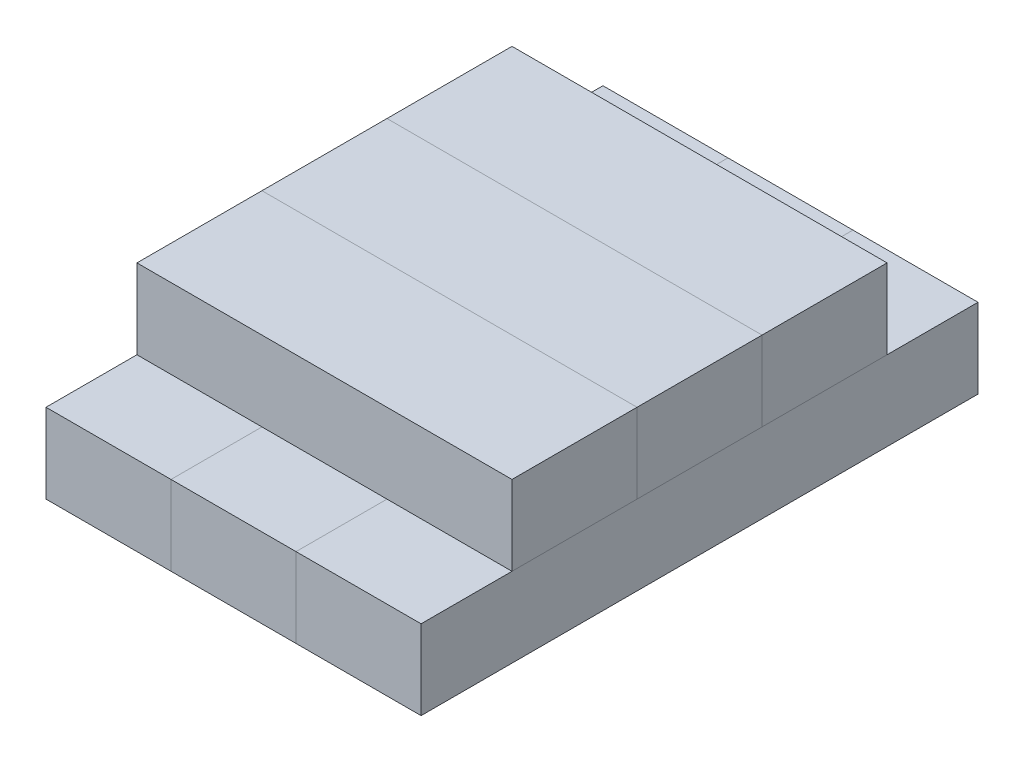
SolidWorks part; units mm, degrees
other "Markup1"
sketch "Sketch3" plane through (419.1, 177.8, 622.3) normal (0.8218, 0.5697, 0.0127) x (-0.0081, 0.0339, -0.9994)
material "Pine"
ref_plane "Front Plane" through (0, 0, 0) normal (0, 0, 1) x (1, 0, 0)
ref_plane "Top Plane" through (0, 0, 0) normal (0, 1, 0) x (1, 0, 0)
ref_plane "Right Plane" through (0, 0, 0) normal (1, 0, 0) x (0, 0, -1)
sketch "Sketch1" plane through (0, 0, 0) normal (0, 0, 1) x (1, 0, 0)
  line L1 (0, 0) -> (139.7, 0)
  line L2 (0, 0) -> (0, 88.9)
  line L3 (0, 88.9) -> (139.7, 88.9)
  line L4 (139.7, 0) -> (139.7, 88.9)
  line L5 (139.7, 0) -> (279.4, 0)
  line L6 (139.7, 0) -> (139.7, 88.9)
  line L7 (139.7, 88.9) -> (279.4, 88.9)
  line L8 (279.4, 0) -> (279.4, 88.9)
  line L9 (279.4, 0) -> (419.1, 0)
  line L10 (279.4, 0) -> (279.4, 88.9)
  line L11 (279.4, 88.9) -> (419.1, 88.9)
  line L12 (419.1, 0) -> (419.1, 88.9)
  dimension "D1" = 88.9
  dimension "D2" = 139.7
  dimension "D3" = 139.7
  dimension "D4" = 139.7
extrude "Boss-Extrude1" add sketch "Sketch1" along normal blind 622.3 contours L1 L4 L3 L2 | L9 L12 L11 L8 region at (69.85, 44.45, 0) region at (349.25, 44.45, 0)
extrude "Boss-Extrude2" add sketch "Sketch1<4>" along normal up to surface (622.3 mm away) separate body contours L5 L8 L7 L4 region at (209.55, 44.45, 0) up to face at (69.85, 44.45, 622.3)
sketch "Sketch1<4>" plane through (0, 0, 0) normal (0, 0, 1) x (1, 0, 0) same geometry as "Sketch1"
sketch "Sketch2" plane through (0, 0, 0) normal (1, 0, 0) x (0, 0, -1)
  line L0 (-622.3, 88.9) -> (0, 88.9) construction
  line L1 (-520.7, 88.9) -> (-381, 88.9)
  line L2 (-520.7, 88.9) -> (-520.7, 177.8)
  line L3 (-520.7, 177.8) -> (-381, 177.8)
  line L4 (-381, 88.9) -> (-381, 177.8)
  line L5 (-622.3, 0) -> (-622.3, 88.9) construction
  dimension "D1" = 88.9
  dimension "D2" = 139.7
  dimension "D3" = 101.6
extrude "Boss-Extrude3" add sketch "Sketch2" along normal up to surface (419.1 mm away) separate body up to face at (419.1, 44.45, 311.15)
pattern_linear "LPattern1" count 3 spacing 139.7 along (0, 0, -1) of "Boss-Extrude3"
